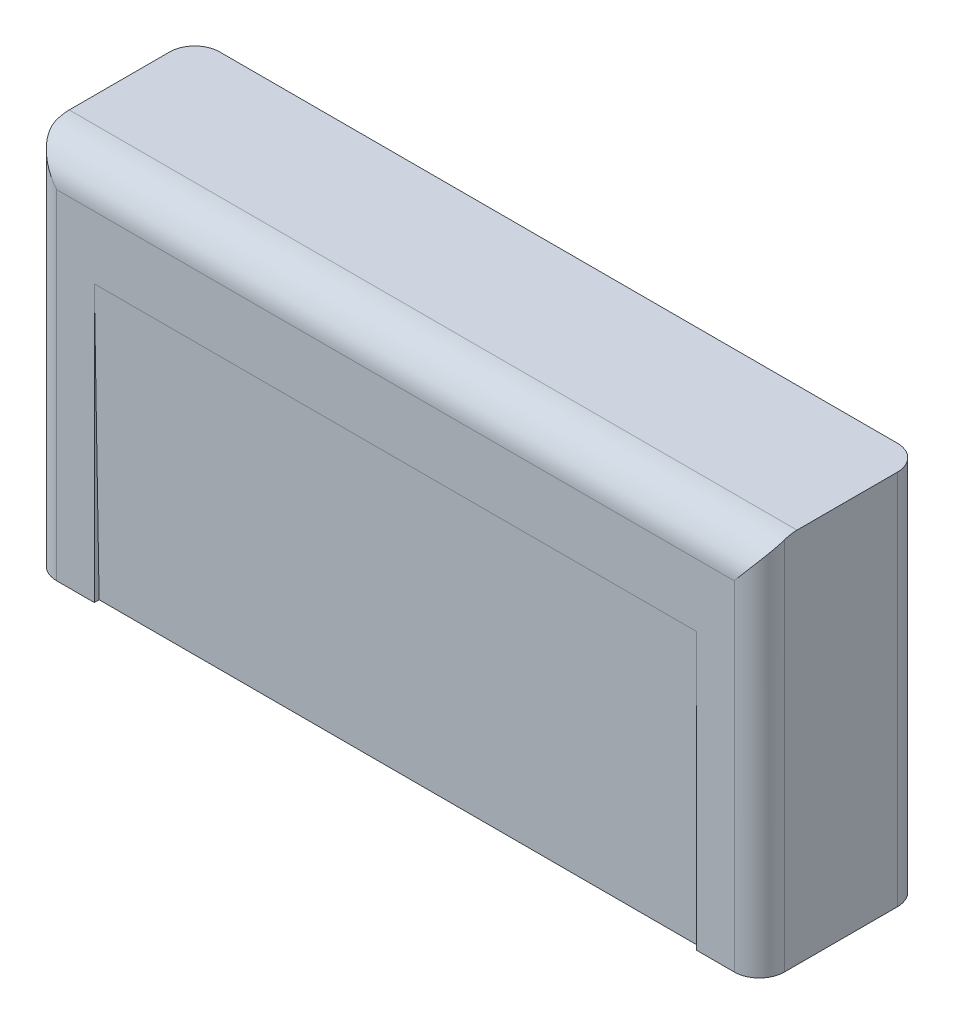
SolidWorks part; units mm, degrees
material "K110"
ref_plane "Front Plane" through (0, 0, 0) normal (0, 0, 1) x (1, 0, 0)
ref_plane "Top Plane" through (0, 0, 0) normal (0, 1, 0) x (1, 0, 0)
ref_plane "Right Plane" through (0, 0, 0) normal (1, 0, 0) x (0, 0, -1)
sketch "Sketch1" plane through (0, 0, 0) normal (0, 1, 0) x (1, 0, 0)
  line L1 (-29, -6.5) -> (29, -6.5)
  line L2 (-29, -6.5) -> (-29, 6.5)
  line L3 (-29, 6.5) -> (29, 6.5)
  line L4 (29, -6.5) -> (29, 6.5)
  line L5 (-29, -6.5) -> (29, 6.5) construction
  line L6 (-29, 6.5) -> (29, -6.5) construction
  point P0 (0, 0)
  dimension "D1" = 13
  dimension "D2" = 58
extrude "Boss-Extrude1" add sketch "Sketch1" against normal blind 30
fillet "Fillet1" radius 2 4 edges at (-29, -15, -6.5) (-29, -15, 6.5) (29, -15, -6.5) (29, -15, 6.5)
fillet "Fillet2" radius 3 1 edges at (0, 0, 6.5) tangent propagation no
hole_wizard "M6 Tapped Hole1" positions "Sketch4" profile "Sketch3" tap size "M6" standard "ISO"
sketch "Sketch4" plane through (0, -30, 0) normal (0, -1, 0) x (-1, 0, 0)
  line L0 (-29, -4.5) -> (-29, 4.5) construction
  line L1 (29, 4.5) -> (29, -4.5) construction
  point P0 (-21.5, 0)
  point P2 (21.5, 0)
  dimension "D1" = 7.5
  dimension "D2" = 7.5
sketch "Sketch3" plane through (21.5, -30, 0) normal (1, 0, 0) x (0, 0, -1)
  line L0 (0, 0) -> (0, 18.5022)
  line L1 (0, 18.5022) -> (2.5, 17)
  line L2 (2.5, 17) -> (2.5, 0.525)
  line L3 (2.5, 0.525) -> (3.025, 0)
  line L5 (3.025, 0) -> (0, 0)
  line L6 (-2.5, 0.525) -> (-3.025, 0) construction
  line L10 (0, 18.5022) -> (-2.5, 17) construction
  line L11 (0, -6.35) -> (0, 107.95) construction
  dimension "Tap Drill Dia." = 5
  dimension "Tap Drill Depth" = 17
  dimension "Near C'Sink Dia." = 6.05
  dimension "Near C'Sink Angle" = 90
  dimension "Drill Angle" = 118
cosmetic thread "Hole Thread1"
cosmetic thread "Hole Thread2"
sketch "Sketch5" plane through (0, 0, 0) normal (1, 0, 0) x (0, 0, -1)
  line L4 (-6.5, -8) -> (-6.116, -30)
  line L5 (-6.5, -30) -> (-6.5, -3) construction
  line L6 (-6.5, -30) -> (-4.5, -30) construction
  line L7 (-6.116, -30) -> (-6.5, -30)
  line L8 (-6.5, -30) -> (-6.5, -8)
  dimension "D1" = 5
  dimension "D2" = 1
extrude "Cut-Extrude1" cut sketch "Sketch5" against normal mid plane 48
